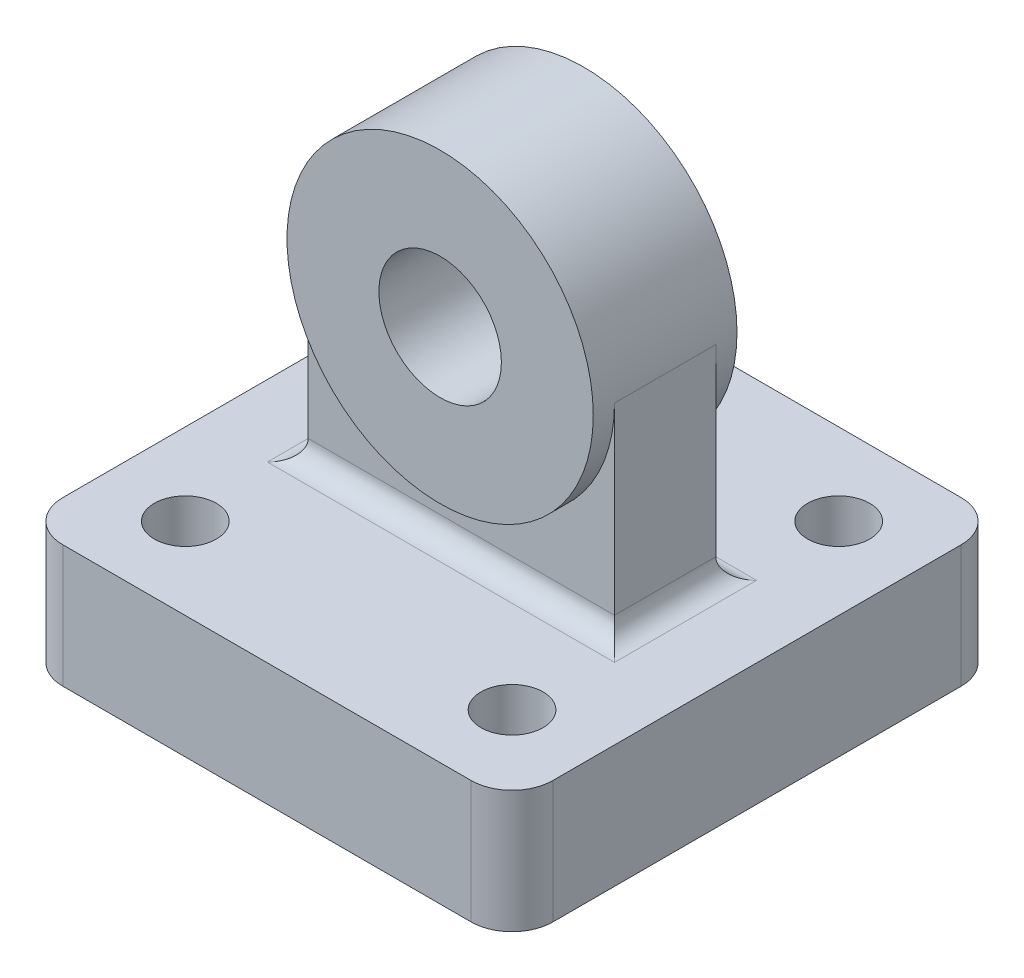
SolidWorks part; units mm, degrees
ref_plane "Front Plane" through (0, 0, 0) normal (0, 0, 1) x (1, 0, 0)
ref_plane "Top Plane" through (0, 0, 0) normal (0, 1, 0) x (1, 0, 0)
ref_plane "Right Plane" through (0, 0, 0) normal (1, 0, 0) x (0, 0, -1)
sketch "Sketch1" plane through (0, 0, 0) normal (0, 1, 0) x (1, 0, 0)
  line L0 (0, -38.1) -> (76.2, -38.1) construction
  line L1 (0, 0) -> (76.2, 0)
  line L2 (0, 0) -> (0, -76.2)
  line L3 (0, -76.2) -> (76.2, -76.2)
  line L4 (76.2, 0) -> (76.2, -76.2)
  line L5 (38.1, 0) -> (38.1, -76.2) construction
  circle A0 centre (63.5, -63.5) radius 4.826
  circle A1 centre (12.7, -63.5) radius 4.826
  circle A2 centre (63.5, -12.7) radius 4.826
  circle A3 centre (12.7, -12.7) radius 4.826
  dimension "D2" = 9.652
  dimension "D1" = 76.2
  dimension "D3" = 12.7
  dimension "D4" = 12.7
extrude "Boss-Extrude1" add sketch "Sketch1" along normal blind 19.05
ref_plane "Plane1" through (0, 0, 38.1) normal (0, 0, 1) x (1, 0, 0)
sketch "Sketch2" plane through (0, 0, 38.1) normal (0, 0, 1) x (1, 0, 0)
  line L0 (0, 19.05) -> (76.2, 19.05) construction
  line L1 (14.2875, 50.8) -> (14.2875, 19.05)
  line L2 (61.9125, 50.8) -> (61.9125, 19.05)
  line L3 (14.2875, 19.05) -> (61.9125, 19.05)
  circle A0 centre (38.1, 50.8) radius 9.525
  circle A1 centre (38.1, 50.8) radius 23.8125
  point P9 (38.1, 19.05)
  dimension "D1" = 19.05
  dimension "D2" = 47.625
  dimension "D3" = 31.75
extrude "Boss-Extrude4" add sketch "Sketch2" along normal mid plane 15.748 contours A1 L1 L3 L2 region at (38.1, 26.6563, 38.1)
extrude "Boss-Extrude5" add sketch "Sketch2<5>" along normal mid plane 22.352 contours A1 A0 region at (38.1, 73.939, 38.1)
sketch "Sketch2<5>" plane through (0, 0, 38.1) normal (0, 0, 1) x (1, 0, 0) same geometry as "Sketch2"
fillet "Fillet1" radius 3.175 4 edges at (38.1, 19.05, 30.226) (14.2875, 19.05, 38.1) (38.1, 19.05, 45.974) (61.9125, 19.05, 38.1)
fillet "Fillet2" radius 6.35 4 edges at (76.2, 9.525, 76.2) (0, 9.525, 76.2) (76.2, 9.525, 0) (0, 9.525, 0)
